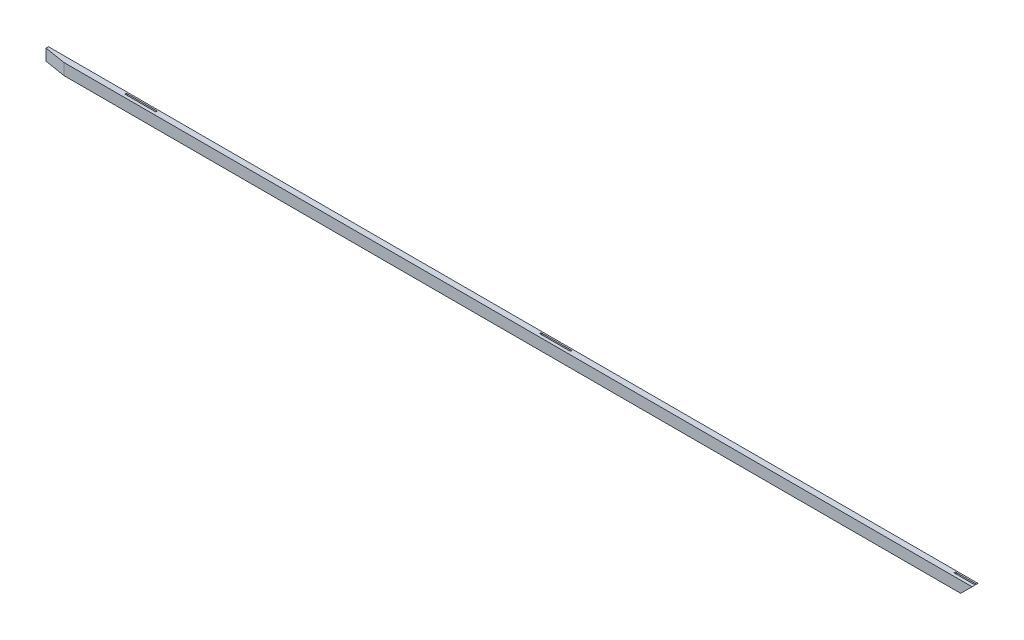
SolidWorks part; units mm, degrees
ref_plane "前视基准面" through (0, 0, 0) normal (0, 0, 1) x (1, 0, 0)
ref_plane "上视基准面" through (0, 0, 0) normal (0, 1, 0) x (1, 0, 0)
ref_plane "右视基准面" through (0, 0, 0) normal (1, 0, 0) x (0, 0, -1)
sketch "草图1" plane through (0, 0, 0) normal (0, 0, 1) x (1, 0, 0)
  line L0 (0, 24) -> (0, -24)
  line L1 (0, -24) -> (3875, -24)
  line L2 (3875, -24) -> (3923, 24)
  line L3 (3923, 24) -> (0, 24)
  point P4 (0, 0)
  dimension "D1" = 3923
  dimension "D2" = 45
  dimension "D3" = 48
extrude "凸台-拉伸1" add sketch "草图1" along normal blind 25
sketch "草图2" plane through (0, -24, 0) normal (0, -1, 0) x (1, 0, 0)
  line L0 (2092.5, 12) -> (2092.5, 6)
  line L1 (2092.5, 6) -> (2207.5, 6)
  line L2 (2207.5, 6) -> (2207.5, 12)
  line L3 (2207.5, 12) -> (2092.5, 12)
  line L4 (0, 0) -> (3875, 0) construction
  line L5 (3923, 25) -> (3923, 0) construction
  point P8 (2150, 12)
  dimension "D1" = 115
  dimension "D2" = 6
  dimension "D3" = 6
  dimension "D4" = 1773
extrude "切除-拉伸1" cut sketch "草图2" against normal blind 7.5
draft "拔模1" type of draft neutral plane draft angle 45 faces to draft 2 face at (2207.5, -20.25, 9) face at (2092.5, -20.25, 9) neutral plane through (0, -16.5, 0) neutral plane normal (0, -1, 0) parameters "D1"=45
mirror "镜向1" about plane through (0, 0, 0) normal (0, 1, 0) of face at (2150, -20.25, 12) of face at (2211.25, -20.25, 9) of face at (2088.75, -20.25, 9) of face at (2150, -16.5, 9) of face at (2150, -20.25, 6)
pattern_linear "阵列(线性)1" count 2 spacing 1750 along (-1, 0, 0) of face at (2150, -16.5, 9) of face at (2088.75, -20.25, 9) of face at (2150, -20.25, 12) of face at (2211.25, -20.25, 9) of face at (2150, -20.25, 6) of face at (2150, 20.25, 12) of face at (2088.75, 20.25, 9) of face at (2150, 16.5, 9) of face at (2211.25, 20.25, 9) of face at (2150, 20.25, 6)
sketch "草图4" plane through (0, 0, 25) normal (0, 0, 1) x (1, 0, 0)
  line L0 (3833.5, 24) -> (3841, 16.5)
  line L1 (3923, 24) -> (0, 24) construction
  line L2 (3841, 16.5) -> (3915.5, 16.5)
  line L3 (3875, -24) -> (3923, 24) construction
  line L4 (3915.5, 16.5) -> (3923, 24)
  line L5 (3923, 24) -> (3833.5, 24)
  line L6 (3833.5, -24) -> (3841, -16.5)
  line L7 (0, -24) -> (3875, -24) construction
  line L8 (3841, -16.5) -> (3882.5, -16.5)
  line L9 (3882.5, -16.5) -> (3875, -24)
  line L10 (3875, -24) -> (3833.5, -24)
  dimension "D1" = 82
  dimension "D2" = 34
  dimension "D3" = 45
  dimension "D4" = 7.5
  dimension "D5" = 7.5
  dimension "D6" = 45
extrude "切除-拉伸2" cut sketch "草图4" against normal blind 6 from offset 13 offset against normal yes
sketch "草图5" plane through (0, -24, 0) normal (0, -1, 0) x (1, 0, 0)
  line L0 (0, 10) -> (90, 25)
  line L1 (0, 25) -> (0, 0) construction
  line L2 (0, 25) -> (3875, 25) construction
  line L3 (90, 25) -> (0, 25)
  line L4 (0, 25) -> (0, 10)
  dimension "D1" = 10
  dimension "D2" = 90
extrude "切除-拉伸3" cut sketch "草图5" against normal up to next
